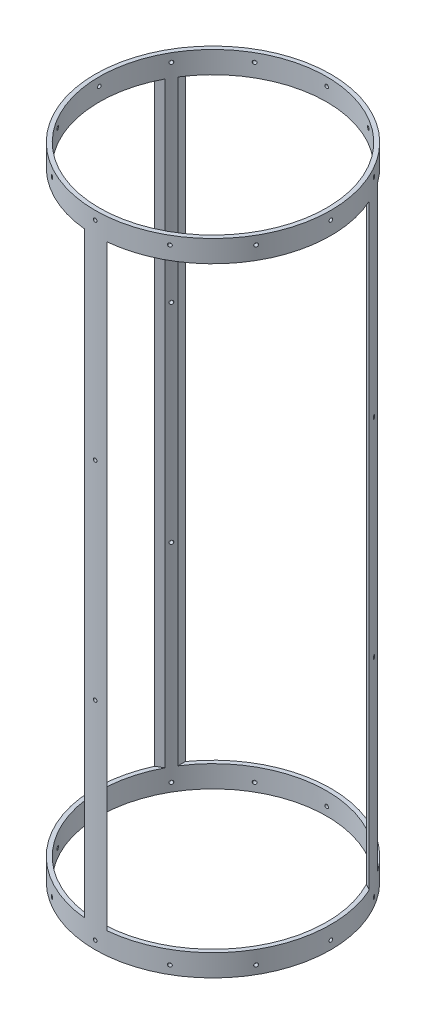
SolidWorks part; units mm, degrees
material "6061-T6 (SS)"
ref_plane "Front Plane" through (0, 0, 0) normal (0, 0, 1) x (1, 0, 0)
ref_plane "Top Plane" through (0, 0, 0) normal (0, 1, 0) x (1, 0, 0)
ref_plane "Right Plane" through (0, 0, 0) normal (1, 0, 0) x (0, 0, -1)
sketch "Sketch1" plane through (0, 0, 0) normal (0, 1, 0) x (1, 0, 0)
  circle A0 centre (0, 0) radius 88.9
  circle A1 centre (0, 0) radius 85.725
  dimension "D1" = 177.8
  dimension "D2" = 171.45
extrude "Boss-Extrude1" add sketch "Sketch1" along normal mid plane 482.854
sketch "Sketch2" plane through (0, 0, 0) normal (0, 0, 1) x (1, 0, 0)
  line L0 (85.725, 241.427) -> (-85.725, 241.427) construction
  line L1 (-72.39, -224.917) -> (72.39, -224.917)
  line L2 (-72.39, -224.917) -> (-72.39, 224.917)
  line L3 (-72.39, 224.917) -> (72.39, 224.917)
  line L4 (72.39, -224.917) -> (72.39, 224.917)
  line L5 (-72.39, -224.917) -> (72.39, 224.917) construction
  line L6 (-72.39, 224.917) -> (72.39, -224.917) construction
  line L7 (88.9, -241.427) -> (88.9, 241.427) construction
  point P0 (0, 0)
  dimension "D1" = 16.51
  dimension "D2" = 16.51
extrude "Cut-Extrude1" cut sketch "Sketch2" against normal up to surface (51.6033 mm away) up to face at (0, 241.427, 88.9)
pattern_circular "CirPattern1" count 3 over 360 about axis through (0, 241.427, 0) along (0, -1, 0) of "Cut-Extrude1"
ref_plane "Plane1" through (88.9, 0, 0) normal (1, 0, 0) x (0, 0, -1)
sketch "Sketch4" plane through (88.9, 0, 0) normal (1, 0, 0) x (0, 0, -1)
  line L0 (0, 97.79) -> (0, -97.79) construction
  line L1 (88.9, 241.427) -> (-88.9, 241.427) construction
  circle A0 centre (0, 235.077) radius 1.3525
  dimension "D1" = 2.7051
  dimension "D2" = 6.35
extrude "Cut-Extrude3" cut sketch "Sketch4" against normal blind 15.24
pattern_circular "CirPattern3" count 12 over 360 about axis through (0, 241.427, 0) along (0, -1, 0) of "Cut-Extrude3"
mirror "Mirror1" about plane through (0, 0, 0) normal (0, 1, 0) of "Cut-Extrude3", "CirPattern3"
ref_plane "Plane2" through (0, 0, 88.9) normal (0, 0, 1) x (1, 0, 0)
sketch "Sketch5" plane through (0, 0, 88.9) normal (0, 0, 1) x (1, 0, 0)
  circle A0 centre (0, 78.359) radius 1.3526
  circle A1 centre (0, -78.359) radius 1.3526
  circle A2 centre (0, -235.077) radius 1.3525 construction
  circle A3 centre (0, 235.077) radius 1.3525 construction
  dimension "D1" = 156.718
  dimension "D2" = 156.718
  dimension "D3" = 2.7051
  dimension "D4" = 2.7051
extrude "Cut-Extrude4" cut sketch "Sketch5" against normal blind 22.86
pattern_circular "CirPattern4" count 3 over 360 about axis through (0, 241.427, 0) along (0, -1, 0) of "Cut-Extrude4"
